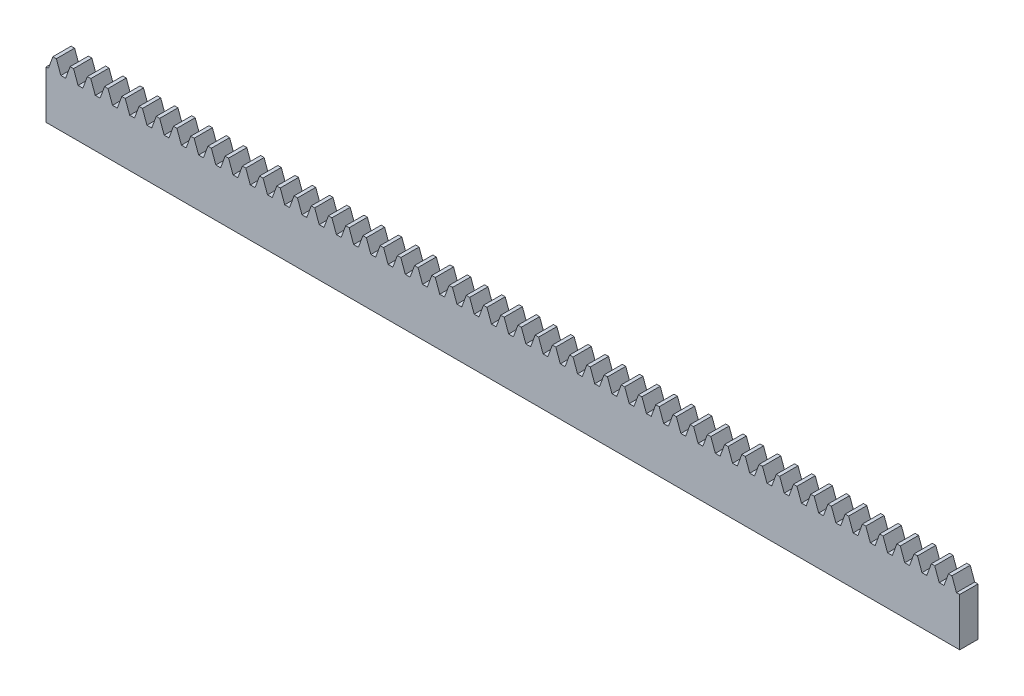
SolidWorks part; units mm, degrees
extrude "Blank" add sketch "BlankSke" against normal blind 5
sketch "BlankSke" plane through (0, 0, 0) normal (0, 0, 1) x (1, 0, 0)
  line L1 (0, 0) -> (250, 0)
  line L2 (0, 0) -> (0, 16.5)
  line L3 (0, 16.5) -> (250, 16.5)
  line L4 (250, 0) -> (250, 16.5)
  dimension "Length" = 250
ref_plane "Plane1" through (0, 0, 0) normal (0, 0, 1) x (1, 0, 0)
ref_plane "Plane2" through (0, 0, 0) normal (0, 1, 0) x (1, 0, 0)
ref_plane "Plane3" through (0, 0, 0) normal (1, 0, 0) x (0, 0, -1)
other "Configuration Table"
sketch "HoldingSke" plane through (0, 0, 0) normal (0, 1, 0) x (1, 0, 0)
  line L0 (0, 0) -> (9.2782, 66.0179)
  line L1 (-15, 0) -> (100, 0) construction
  line L2 (0, 0) -> (-2.1039, 2.3779)
  line L3 (0, 0) -> (-11.863, 4.5341)
  line L4 (0, 0) -> (4.9534, 7.0742)
  line L5 (0, 0) -> (-23.7986, -8.8762)
  line L6 (0, 0) -> (-10.5278, -7.1032)
  line L9 (-71.009, 38.7566) -> (163.9142, 124.2616)
  line L10 (-76.2, 3.8779) -> (-61.2, 3.8779)
  line L11 (0, 0) -> (-5, 0)
  line L12 (-76.2, 101.6) -> (-76.147, 101.6)
  line L13 (24.9733, 27.94) -> (52.9518, 28.4284)
  line L14 (24.9733, 27.94) -> (24.9743, 27.94)
  line L15 (24.9733, 27.94) -> (100.4006, 29.5858)
  circle A0 centre (0, 0) radius 19.05
  circle A1 centre (0, 0) radius 7.5
  circle A2 centre (0, 0) radius 12.7
  dimension "Num_teeth" = 55
  dimension "Width" = 5
  dimension "Length" = 250
  dimension "Pitch_height" = 15
sketch "TooCutSkeIll" plane through (0, 0, 0) normal (0, 0, 1) x (1, 0, 0)
  line L0 (-1.8687, 16.4605) -> (-0.7447, 13.3724)
  line L1 (-0.3914, 13.125) -> (0.3914, 13.125)
  line L2 (0.7447, 13.3724) -> (1.8687, 16.4605)
  line L3 (250, 16.5) -> (0, 16.5) construction
  line L4 (0, 0) -> (0, 64.897) construction
  line L5 (-13.208, 15) -> (12.954, 15) construction
  line L6 (0, 0) -> (250, 0) construction
  line L7 (1.3371, 15) -> (1.3371, 48.7463) construction
  line L8 (-1.3371, 15) -> (-1.3371, 48.7463) construction
  line L9 (1.9251, 16.5) -> (1.9251, 16.754)
  line L10 (-1.9251, 16.5) -> (-1.9251, 16.754)
  line L11 (-1.9251, 16.754) -> (1.9251, 16.754)
  arc A0 (0.3914, 13.125) -> (0.7447, 13.3724) centre (0.3914, 13.501) ccw
  arc A1 (-0.7447, 13.3724) -> (-0.3914, 13.125) centre (-0.3914, 13.501) ccw
  arc A2 (1.9251, 16.5) -> (1.8687, 16.4605) centre (1.9251, 16.44) ccw
  arc A3 (-1.8687, 16.4605) -> (-1.9251, 16.5) centre (-1.9251, 16.44) ccw
  dimension "Addendum_plus" = 1.754
  dimension "Pitch_height" = 15
  dimension "Pressure_angle" = 20
  dimension "Gap_width" = 2.6742
  dimension "Dedendum" = 1.875
extrude "ToothCutIll" [suppressed] cut sketch "TooCutSkeIll" against normal through all
sketch "TooCutSkeSim" plane through (0, 0, 0) normal (0, 0, 1) x (1, 0, 0)
  line L0 (0.6547, 13.125) -> (-0.6547, 13.125)
  line L1 (1.9755, 16.754) -> (0.6547, 13.125)
  line L2 (0, 17.4625) -> (0, 53.467) construction
  line L3 (1.9755, 16.754) -> (-1.9755, 16.754)
  line L6 (-1.9755, 16.754) -> (-0.6547, 13.125)
  line L9 (-1.3371, 15) -> (1.3371, 15) construction
  line L10 (0, 0) -> (250, 0) construction
  line L11 (1.3371, 15) -> (1.3371, 53.467) construction
  line L12 (-1.3371, 15) -> (-1.3371, 53.467) construction
  dimension "Addendum_plus" = 1.754
  dimension "Pitch_height" = 15
  dimension "Pressure_angle" = 20
  dimension "Gap_width" = 2.6742
  dimension "Dedendum" = 1.875
extrude "ToothCutSim" cut sketch "TooCutSkeSim" against normal through all
pattern_linear "TeethCuts" count 55 spacing 4.7124 along (1, 0, 0) of "ToothCutIll", "ToothCutSim"
equation "' \"Module@HoldingSke\" = 6.35"
equation "' \"Num_teeth@HoldingSke\" = 12"
equation "' \"Ap@HoldingSke\" =  20"
equation "' \"Ap@HoldingSke\" = 20"
equation "' \"Width@HoldingSke\" = 0.25 * 25.4"
equation "' \"Show_teeth@HoldingSke\" = 500"
equation "' \"Backlash@HoldingSke\" = 0.009 * 25.4"
equation "' \"Addendum_fac@HoldingSke\" = 1.0"
equation "' \"Dedendum_fac@HoldingSke\" = 1.25"
equation "' \"Dedendum_add@HoldingSke\" = 0.00005 * 25.4"
equation "' \"Clearance_fac@HoldingSke\" = 0.25"
equation "' \"Pitch_height@HoldingSke\" = 1 * 25.4"
equation "' \"Length@HoldingSke\" = 4.71 * 25.4"
equation "\"Pitch@HoldingSke\" = 1 / \"Module@HoldingSke\""
equation "\"MPH@HoldingSke\" = \"Dedendum_fac@HoldingSke\" / \"Pitch@HoldingSke\" + 2 * \"Dedendum_add@HoldingSke\" + 0.002 * 25.4"
equation "\"MPH@HoldingSke\" = ((sgn( \"MPH@HoldingSke\" - \"Pitch_height@HoldingSke\")+1)*( \"MPH@HoldingSke\" - \"Pitch_height@HoldingSke\"))/2 + \"Pitch_height@HoldingSke\""
equation "\"Blank_height@BlankSke\" = \"Pitch_height@HoldingSke\" + \"Addendum_fac@HoldingSke\"  / \"Pitch@HoldingSke\" "
equation "\"Length@BlankSke\" =  \"Length@HoldingSke\""
equation "\"Face_width@Blank\" = \"Width@HoldingSke\""
equation "\"Pressure_angle@TooCutSkeIll\" = \"Ap@HoldingSke\""
equation "\"Addendum_plus@TooCutSkeIll\" =  \"Addendum_fac@HoldingSke\"  / \"Pitch@HoldingSke\" + 0.001 *25.4"
equation "\"Dedendum@TooCutSkeIll\" = \"Dedendum_fac@HoldingSke\"  / \"Pitch@HoldingSke\""
equation "\"Pitch_height@TooCutSkeIll\" =  \"MPH@HoldingSke\""
equation "\"Gap_width@TooCutSkeIll\" = 3.14159265 / 2 / \"Pitch@HoldingSke\" + 6 * \"Backlash@HoldingSke\""
equation "\"Pressure_angle@TooCutSkeSim\" = \"Ap@HoldingSke\""
equation "\"Addendum_plus@TooCutSkeSim\" =  \"Addendum_fac@HoldingSke\"  / \"Pitch@HoldingSke\" + 0.001 * 25.4"
equation "\"Dedendum@TooCutSkeSim\" = \"Dedendum_fac@HoldingSke\"  / \"Pitch@HoldingSke\""
equation "\"Pitch_height@TooCutSkeSim\" =  \"MPH@HoldingSke\""
equation "\"Gap_width@TooCutSkeSim\" = 3.14159265 / 2 / \"Pitch@HoldingSke\" + 6 * \"Backlash@HoldingSke\""
equation "\"Root_fillet@TooCutSkeIll\" = \"Clearance_fac@HoldingSke\" / \"Pitch@HoldingSke\" + \"Dedendum_add@HoldingSke\""
equation "\"Break_rad@TooCutSkeIll\" = 0.02 / \"Pitch@HoldingSke\" * 2"
equation "\"Linear_pitch@TeethCuts\" = 3.14159265 / \"Pitch@HoldingSke\""
equation "\"Num_teeth@HoldingSke\" = int( ( \"Length@HoldingSke\" + 0 ) / (3.14159265 / \"Pitch@HoldingSke\")) + 0.9999  + 1"
equation " \"Num_teeth@TeethCuts\" = int( \"Show_teeth@HoldingSke\" ) + 1"
equation " \"Num_teeth@TeethCuts\" = ((sgn( \"Num_teeth@TeethCuts\" - \"Num_teeth@HoldingSke\" )-1)*( \"Num_teeth@TeethCuts\" - \"Num_teeth@HoldingSke\" ))/-2+ \"Num_teeth@HoldingSke\""
equation " \"Num_teeth@TeethCuts\" = ((sgn( \"Num_teeth@TeethCuts\" - 2.0)+1)*( \"Num_teeth@TeethCuts\" - 2.0))/2 +2.0"
